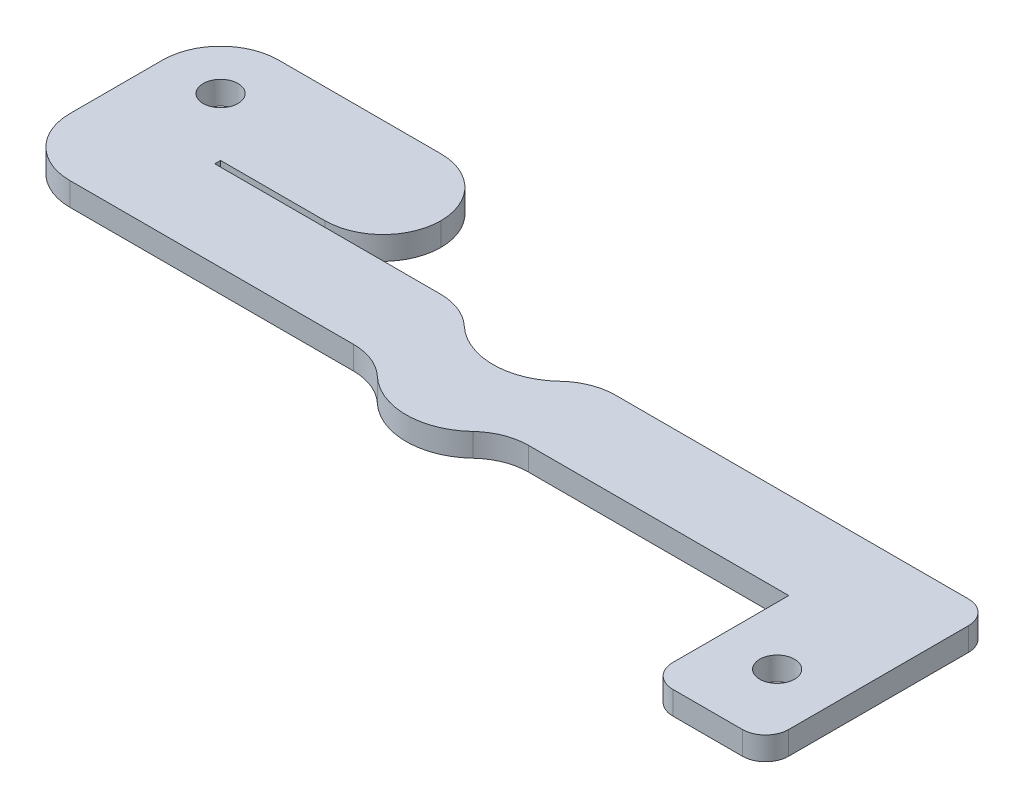
SolidWorks part; units mm, degrees
ref_plane "前视基准面" through (0, 0, 0) normal (0, 0, 1) x (1, 0, 0)
ref_plane "上视基准面" through (0, 0, 0) normal (0, 1, 0) x (1, 0, 0)
ref_plane "右视基准面" through (0, 0, 0) normal (1, 0, 0) x (0, 0, -1)
sketch "草图1" plane through (0, 0, 0) normal (0, 1, 0) x (1, 0, 0)
  line L0 (0, 73.2303) -> (0, -63.1712) construction
  line L1 (-67.7984, 0) -> (122.52, 0) construction
  line L2 (17.1962, -13) -> (52, -13)
  line L3 (-15, 5) -> (-25, 5)
  line L4 (-25, -13) -> (6.8038, -13)
  line L6 (-25, 5) -> (-25, -13)
  line L8 (-15, -5.5) -> (52, -5.5)
  line L10 (52, -13) -> (52, -5.5)
  line L11 (-15, 5) -> (-15, -5.5)
  circle A0 centre (-20, 0) radius 1.5
  arc A1 (6.8038, -13) -> (17.1962, -13) centre (12, -10) ccw
  dimension "D7" = 3
  dimension "D8" = 40
  dimension "D3" = 25
  dimension "D4" = 12
  dimension "D1" = 10
  dimension "D2" = 18
  dimension "D5" = 10.5
  dimension "D6" = 67
  dimension "D9" = 5
  dimension "D10" = 3
  dimension "D11" = 5
extrude "凸台-拉伸1" add sketch "草图1" along normal blind 2
fillet "圆角2" radius 5 1 edges at (-25, 1, -5)
fillet "圆角3" radius 5 1 edges at (-25, 1, 13)
sketch "草图7" plane through (0, 2, 0) normal (0, 1, 0) x (1, 0, 0)
  line L0 (52, -13) -> (52, -5.5) construction
  line L1 (52, -5.5) -> (-15, -5.5) construction
  circle A0 centre (12, -2.5) radius 6
  dimension "D3" = 12
  dimension "D1" = 40
  dimension "D2" = 3
extrude "切除-拉伸4" cut sketch "草图7" against normal blind 10
fillet "圆角5" radius 5 4 edges at (6.8038, 1, 5.5) (17.1962, 1, 5.5) (17.1962, 1, 13) (6.8038, 1, 13)
sketch "草图8" plane through (0, 0, 13) normal (0, 0, 1) x (1, 0, 0)
  line L0 (19.5498, 2) -> (52, 2) construction
  line L1 (52, 0) -> (42, 0)
  line L2 (52, 0) -> (52, 2)
  line L3 (52, 2) -> (42, 2)
  line L4 (42, 0) -> (42, 2)
  dimension "D1" = 10
extrude "凸台-拉伸3" add sketch "草图8" along normal blind 12
sketch "草图9" plane through (0, 2, 0) normal (0, 1, 0) x (1, 0, 0)
  line L0 (19.5498, -13) -> (42, -13) construction
  line L1 (47, -25) -> (47, -19) construction
  line L2 (52, -25) -> (42, -25) construction
  circle A0 centre (47, -19) radius 1.5
  dimension "D1" = 3
  dimension "D2" = 6
extrude "切除-拉伸5" cut sketch "草图9" against normal blind 12
fillet "圆角6" radius 2 3 edges at (52, 1, 5.5) (52, 1, 25) (42, 1, 25)
sketch "草图10" plane through (-15, 0, 0) normal (1, 0, 0) x (0, 0, -1)
  line L0 (-5.5, 2) -> (5, 2) construction
  line L1 (5, 0) -> (-5, 0)
  line L2 (5, 0) -> (5, 2)
  line L3 (5, 2) -> (-5, 2)
  line L4 (-5, 0) -> (-5, 2)
  dimension "D1" = 10
extrude "凸台-拉伸4" add sketch "草图10" along normal blind 14
fillet "圆角7" radius 5 1 edges at (-1, 1, 5)
fillet "圆角8" radius 5 1 edges at (-1, 1, -5)
